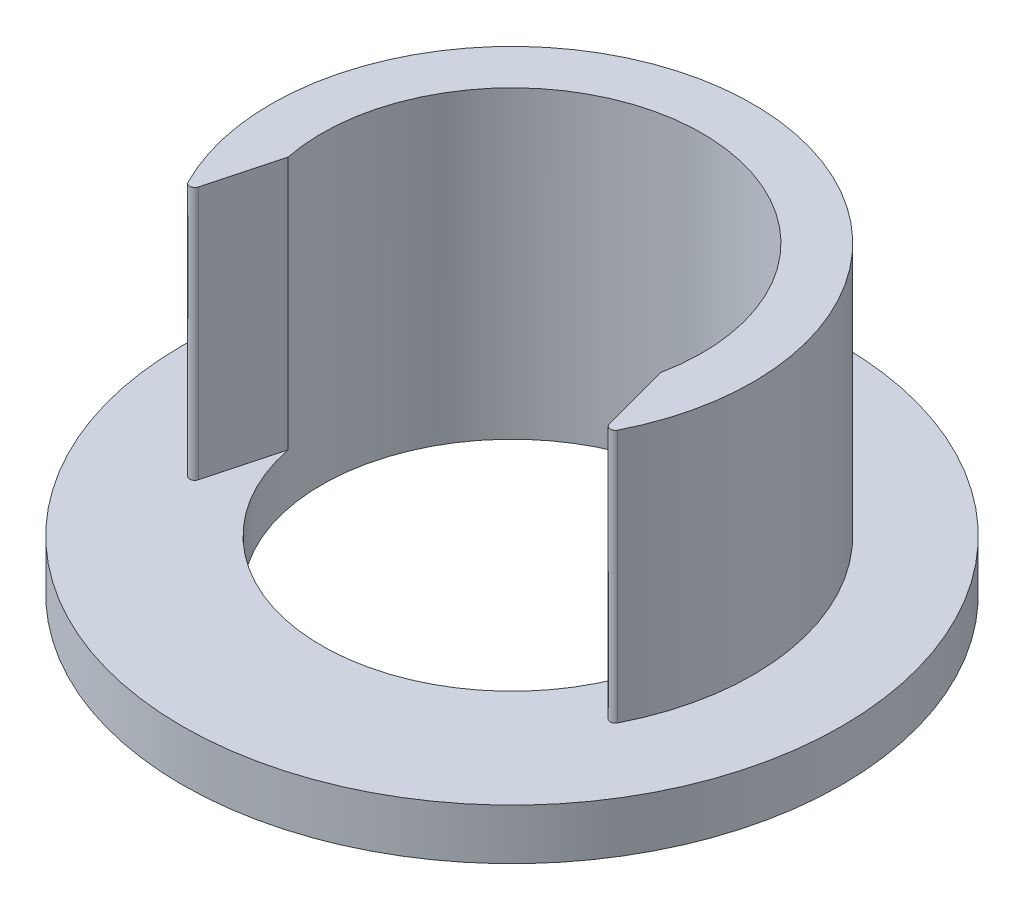
SolidWorks part; units mm, degrees
ref_plane "前基準面" through (0, 0, 0) normal (0, 0, 1) x (1, 0, 0)
ref_plane "上基準面" through (0, 0, 0) normal (0, 1, 0) x (1, 0, 0)
ref_plane "右基準面" through (0, 0, 0) normal (1, 0, 0) x (0, 0, -1)
sketch "草圖2" plane through (0, 0, 0) normal (0, 1, 0) x (1, 0, 0)
  circle A0 centre (0, 0) radius 65
  circle A1 centre (0, 0) radius 37.5
  dimension "D1" = 130
  dimension "D2" = 75
extrude "填料-伸長1" add sketch "草圖2" along normal blind 10
sketch "草圖3" plane through (0, 10, 0) normal (0, 1, 0) x (1, 0, 0)
  line L0 (0, 37.5) -> (0, 0) construction
  line L1 (0, 0) -> (-32.476, -18.75) construction
  line L2 (0, 0) -> (32.476, -18.75) construction
  line L3 (-32.476, -18.75) -> (-41.1362, -23.75)
  line L4 (32.476, -18.75) -> (41.1362, -23.75)
  circle A0 centre (0, 0) radius 37.5 construction
  arc A1 (32.476, -18.75) -> (-32.476, -18.75) centre (0, 0) ccw
  arc A2 (-41.1362, -23.75) -> (41.1362, -23.75) centre (0, 0) cw
  dimension "D1" = 120
  dimension "D2" = 120
  dimension "D3" = 10
  dimension "D4" = 10
extrude "填料-伸長2" add sketch "草圖3" along normal blind 50
chamfer "導角1" distance 10 angle 45 2 edges at (32.476, 35, 18.75) (-32.476, 35, 18.75)
fillet "圓角2" radius 1 2 edges at (41.1362, 35, 23.75) (-41.1362, 35, 23.75)
